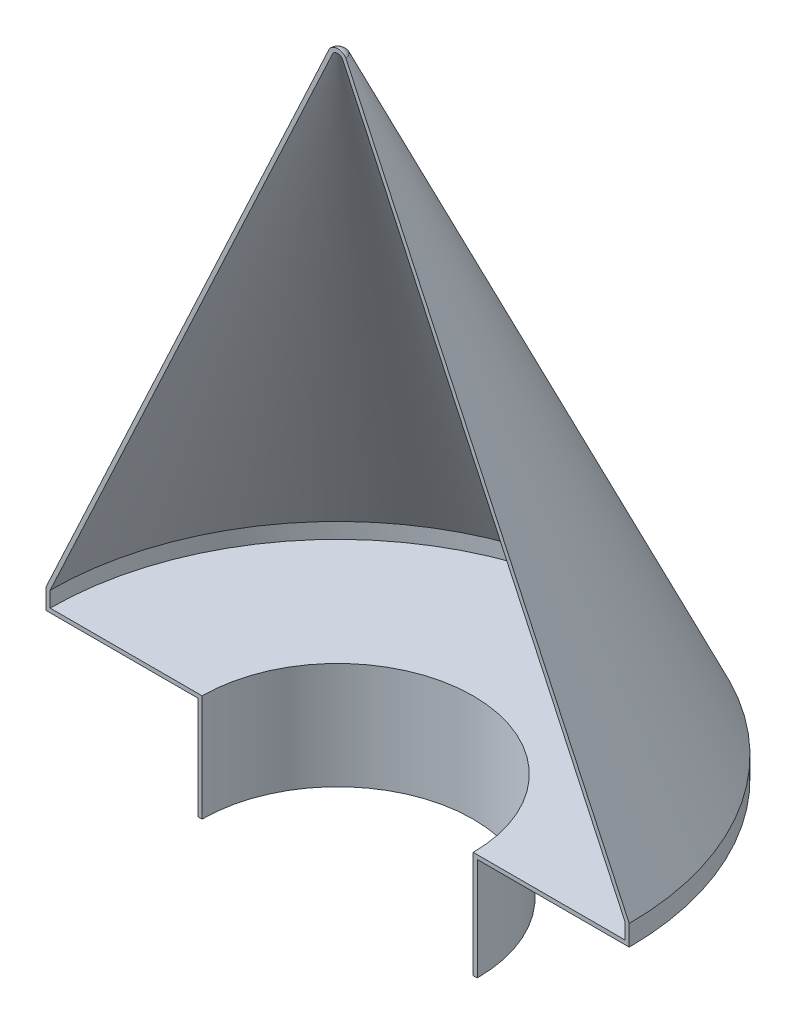
SolidWorks part; units mm, degrees
ref_plane "Front Plane" through (0, 0, 0) normal (0, 0, 1) x (1, 0, 0)
ref_plane "Top Plane" through (0, 0, 0) normal (0, 1, 0) x (1, 0, 0)
ref_plane "Right Plane" through (0, 0, 0) normal (1, 0, 0) x (0, 0, -1)
sketch "Sketch3" plane through (0, 0, 0) normal (0, 0, 1) x (1, 0, 0)
  line L1 (0, 0) -> (0, 307.942)
  line L4 (0, 0) -> (0, -50)
  line L5 (0, -50) -> (68, -50)
  line L6 (68, -50) -> (68, 0)
  line L9 (142, 0) -> (142, 10)
  line L11 (68, 0) -> (142, 0)
  line L12 (4, 305.942) -> (142, 10)
  line L13 (0, 229.1763) -> (0, 65.794) construction
  arc A0 (0, 307.942) -> (4, 305.942) centre (0, 302.942) cw
  point P11 (68, -50)
  point P14 (142, 10)
  dimension "Round yDim" = 2
  dimension "Lip Height" = 10
  dimension "Shoulder Height" = 50
  dimension "Half Angle" = 25
  dimension "Shoulder Diam" = 136
  dimension "Outer Diam" = 284
  dimension "Round xDim" = 8
revolve "Revolve1" add sketch "Sketch3" angle 360 about L1
shell "Shell1" thickness 2 removed face at (0, -50, -68)
sketch "Sketch4" plane through (0, 0, 0) normal (0, 0, 1) x (1, 0, 0)
  line L0 (68, -50) -> (-68, -50)
  line L1 (68, -50) -> (-68, -50)
  line L2 (68, 0) -> (68, -50)
  line L3 (68, 0) -> (68, -50)
  line L4 (142, 0) -> (68, 0)
  line L5 (142, 0) -> (68, 0)
  line L6 (-142, 0) -> (-142, 10)
  line L7 (-142, 0) -> (-142, 10)
  line L8 (-142, 10) -> (-4, 305.942)
  line L9 (-142, 10) -> (-4, 305.942)
  line L10 (4, 305.942) -> (142, 10)
  line L11 (4, 305.942) -> (142, 10)
  line L12 (142, 10) -> (142, 0)
  line L13 (142, 10) -> (142, 0)
  line L14 (-68, 0) -> (-142, 0)
  line L15 (-68, 0) -> (-142, 0)
  line L16 (-68, -50) -> (-68, 0)
  line L17 (-68, -50) -> (-68, 0)
  arc A0 (4, 305.942) -> (-4, 305.942) centre (0, 302.942) ccw
  arc A1 (4, 305.942) -> (-4, 305.942) centre (0, 302.942) ccw
extrude "Cut-Extrude1" cut sketch "Sketch4" along normal through all
